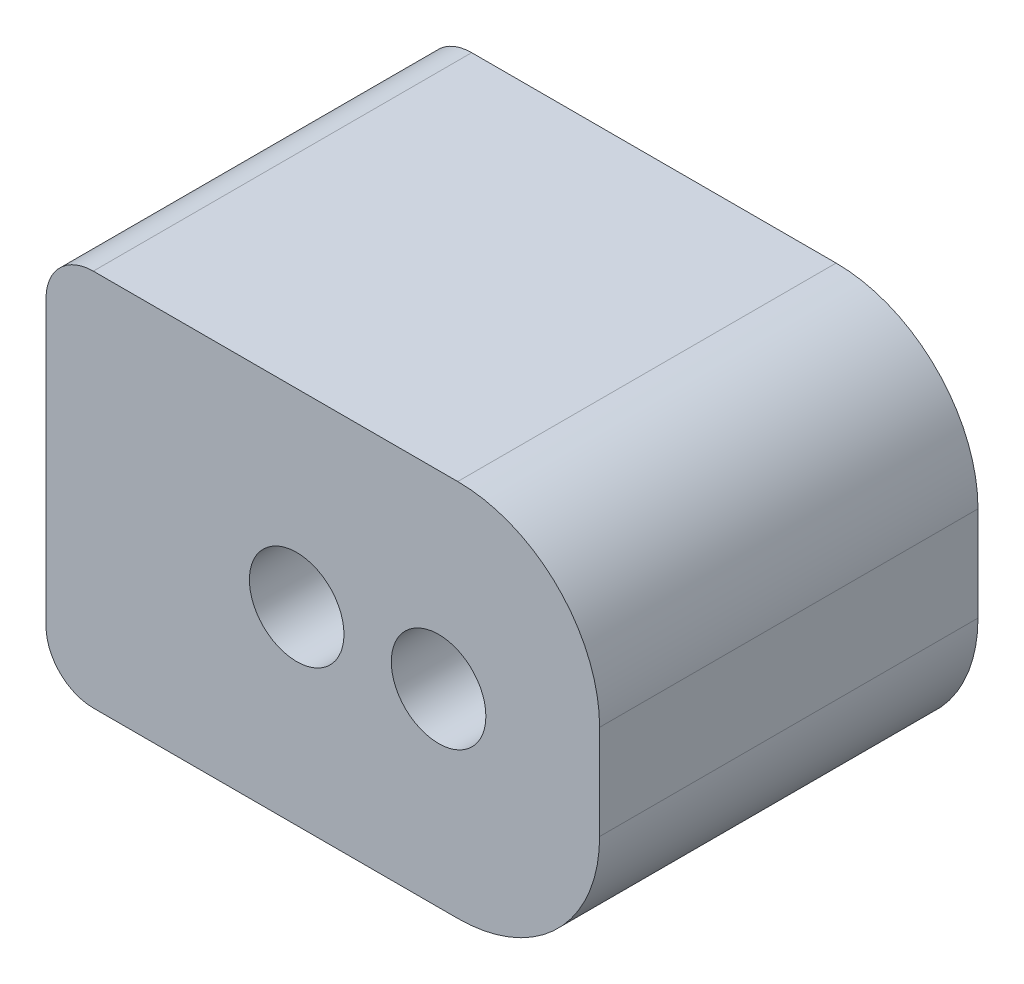
SolidWorks part; units mm, degrees
ref_plane "Front" through (0, 0, 0) normal (0, 0, 1) x (1, 0, 0)
ref_plane "Top" through (0, 0, 0) normal (0, 1, 0) x (1, 0, 0)
ref_plane "Right" through (0, 0, 0) normal (1, 0, 0) x (0, 0, -1)
sketch "Sketch1" plane through (0, 0, 0) normal (0, 0, 1) x (1, 0, 0)
  line L0 (-5.3, 4) -> (0, 4)
  line L1 (0, -4) -> (-5.3, -4)
  line L2 (-5.3, 4) -> (-5.3, -4)
  line L3 (55, 0) -> (-55, 0) construction
  line L4 (0, 4) -> (6.4045, 4)
  line L5 (0, 4) -> (0, -4)
  line L6 (0, -4) -> (6.4045, -4)
  line L7 (6.4045, 4) -> (6.4045, -4)
  circle A0 centre (0, 0) radius 4
  circle A1 centre (0, 0) radius 1
  circle A2 centre (3, 0) radius 1
  dimension "D1" = 8
  dimension "D3" = 2
  dimension "D4" = 3
  dimension "D2" = 5.3
extrude "Boss-Extrude1" add sketch "Sketch1" along normal blind 8 contours A0 L0 L2 L1 | A1 L5 A0 | A1 L5 A0 | A0 A2 L6 L7 L4 region at (-4.0362, 0, 0) region at (1.5952, 0, 0) region at (4.6509, 0, 0) region at (-1.7825, 0, 0)
sketch "Sketch4" plane through (-5.3, 0, 0) normal (-1, 0, 0) x (0, 0, 1)
  line L0 (55, 0) -> (-55, 0) construction
  circle A0 centre (4, 0) radius 3.25
  dimension "D1" = 6.5
extrude "Cut-Extrude3" cut sketch "Sketch4" against normal blind 2.7 from offset 0.8 offset against normal yes
ref_plane "Plane1" through (0, 0, 4) normal (0, 0, 1) x (1, 0, 0)
sketch "Sketch3" plane through (0, 0, 4) normal (0, 0, 1) x (1, 0, 0)
  line L0 (55, 0) -> (-55, 0) construction
  circle A0 centre (-5, 0) radius 3.25
  circle A1 centre (0, 0) radius 1 construction
  dimension "D1" = 6.5
  dimension "D2" = 5
extrude "Cut-Extrude2" [suppressed] cut sketch "Sketch3" against normal mid plane 2.3
fillet "Fillet2" radius 1 2 edges at (-5.3, -4, 4) (-5.3, 4, 4)
fillet "Fillet3" radius 3 2 edges at (6.4045, -4, 4) (6.4045, 4, 4)
